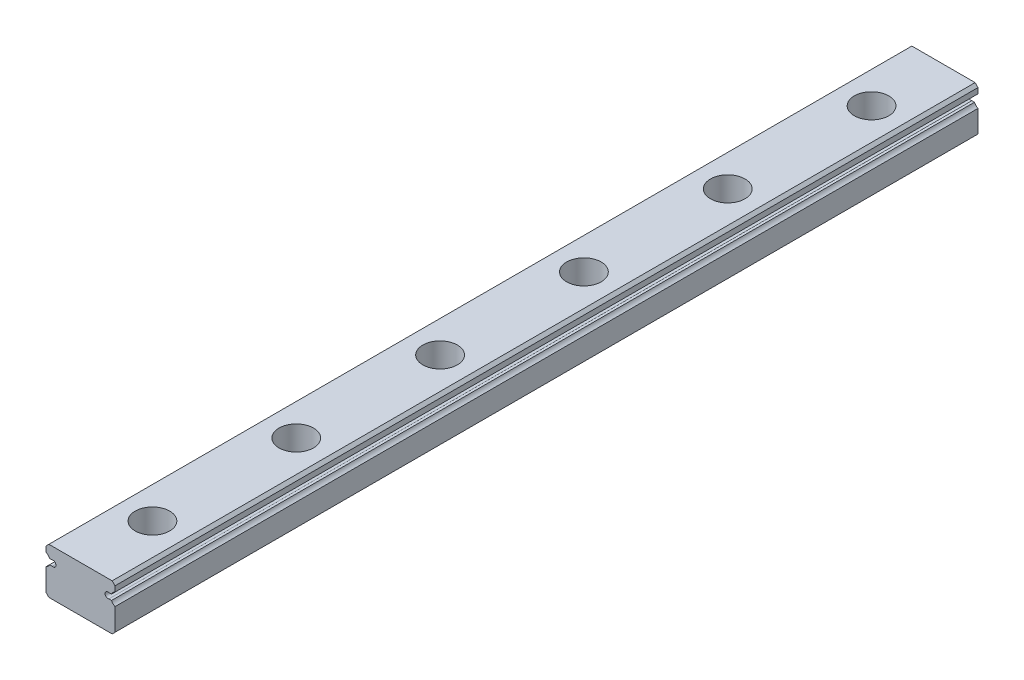
SolidWorks part; units mm, degrees
material "Chrome Stainless Steel"
ref_plane "Front Plane" through (0, 0, 0) normal (0, 0, 1) x (1, 0, 0)
ref_plane "Top Plane" through (0, 0, 0) normal (0, 1, 0) x (1, 0, 0)
ref_plane "Right Plane" through (0, 0, 0) normal (1, 0, 0) x (0, 0, -1)
sketch "Sketch1" plane through (0, 0, 0) normal (0, 0, 1) x (1, 0, 0)
  line L0 (0, 4) -> (0, -4) construction
  line L1 (5.5, -4) -> (-5.5, -4)
  line L2 (-5.5, -4) -> (-6, -3.5)
  line L3 (-6, -3.5) -> (-6, 0.3689)
  line L4 (5.5, 4) -> (-5.5, 4)
  line L5 (-5.5, 4) -> (-6, 3.5)
  line L6 (-6, 2.5511) -> (-6, 3.5)
  line L7 (-5.3839, 0.985) -> (-4.9211, 0.985)
  line L8 (-5.3839, 1.935) -> (-4.9211, 1.935)
  line L9 (5.3839, 0.985) -> (4.9211, 0.985)
  line L10 (5.5, 4) -> (6, 3.5)
  line L11 (6, 2.5511) -> (6, 3.5)
  line L12 (5.3839, 1.935) -> (4.9211, 1.935)
  line L13 (6, -3.5) -> (6, 0.3689)
  line L14 (5.5, -4) -> (6, -3.5)
  circle A0 centre (-6.475, 1.46) radius 1.19 construction
  circle A1 centre (-4.765, 1.46) radius 0.5 construction
  arc A2 (-6, 0.3689) -> (-5.3839, 0.985) centre (-6.475, 1.46) ccw
  arc A3 (-5.3839, 1.935) -> (-6, 2.5511) centre (-6.475, 1.46) ccw
  arc A4 (-4.9211, 0.985) -> (-4.9211, 1.935) centre (-4.765, 1.46) ccw
  arc A5 (5.3839, 1.935) -> (6, 2.5511) centre (6.475, 1.46) cw
  arc A6 (4.9211, 0.985) -> (4.9211, 1.935) centre (4.765, 1.46) cw
  arc A7 (6, 0.3689) -> (5.3839, 0.985) centre (6.475, 1.46) cw
  point P4 (0, 0)
  dimension "D5" = 5.46
  dimension "D6" = 6.475
  dimension "D7" = 2.38
  dimension "D11" = 1
  dimension "D12" = 5.46
  dimension "D13" = 4.765
  dimension "D1" = 8
  dimension "D2" = 0.5
  dimension "D3" = 0.5
  dimension "D4" = 6
  dimension "D8" = 0.5
  dimension "D9" = 0.5
  dimension "D10" = 6
  dimension "D14" = 0.475
  dimension "D15" = 0.475
extrude "Boss-Extrude1" add sketch "Sketch1" along normal blind 150 contours L13 A7 L9 A6 L12 A5 L11 L10 L4 L5 L6 A3 L8 A4 L7 A2 L3 L2 L1 L14 region at (0, -0.0654, 0)
sketch "Sketch2" plane through (0, 4, 0) normal (0, 1, 0) x (1, 0, 0)
  line L0 (5.5, 0) -> (-5.5, 0) construction
  circle A0 centre (0, -12.5) radius 3
  dimension "D1" = 12.5
extrude "Cut-Extrude1" cut sketch "Sketch2" against normal blind 4.5
sketch "Sketch3" plane through (0, -0.5, 0) normal (0, 1, 0) x (1, 0, 0)
  circle A0 centre (0, -12.5) radius 1.75
extrude "Cut-Extrude2" cut sketch "Sketch3" against normal through all
pattern_linear "LPattern1" count 6 spacing 25 along (0, 0, 1) of "Cut-Extrude1", "Cut-Extrude2"
